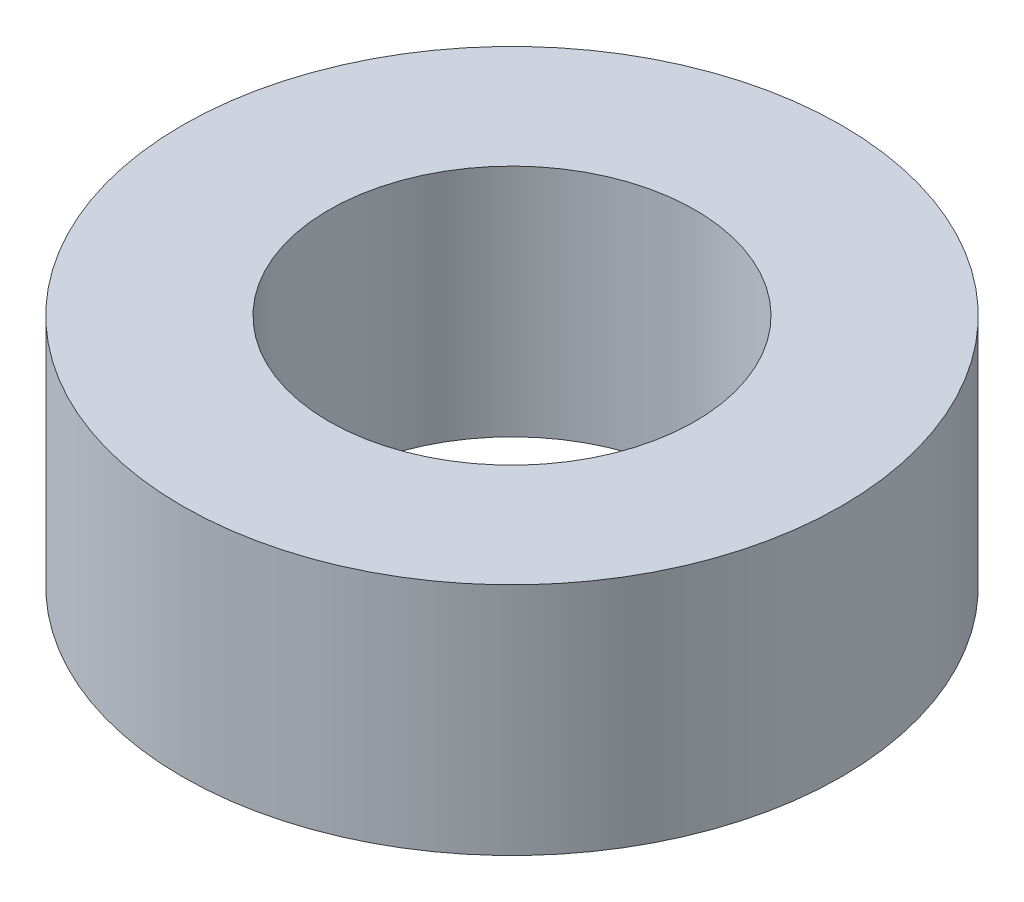
SolidWorks part; units mm, degrees
ref_plane "Front Plane" through (0, 0, 0) normal (0, 0, 1) x (1, 0, 0)
ref_plane "Top Plane" through (0, 0, 0) normal (0, 1, 0) x (1, 0, 0)
ref_plane "Right Plane" through (0, 0, 0) normal (1, 0, 0) x (0, 0, -1)
sketch "Sketch1" plane through (0, 0, 0) normal (0, 1, 0) x (1, 0, 0)
  circle A0 centre (0, 0) radius 22.5
  dimension "FLANGE_OD" = 45
extrude "Boss-Extrude1" add sketch "Sketch1" along normal blind 16
sketch "Sketch2" plane through (0, 0, 0) normal (0, 1, 0) x (1, 0, 0)
  circle A0 centre (0, 0) radius 12.5
  dimension "BORE_D" = 25
extrude "Cut-Extrude1" cut sketch "Sketch2" along normal through all
sketch "Sketch3" plane through (0, 16, 0) normal (0, 1, 0) x (1, 0, 0)
  circle A0 centre (0, 0) radius 7.66 construction
  circle A1 centre (-7.66, 0) radius 1.7659
  dimension "BOLT_D" = 3.5319
  dimension "BOLT_PCD" = 15.3201
extrude "Cut-Extrude2" cut sketch "Sketch3" against normal blind 15.6942 rebuild error yes
pattern_circular "CirPattern1" count 4 over 360 rebuild error yes
